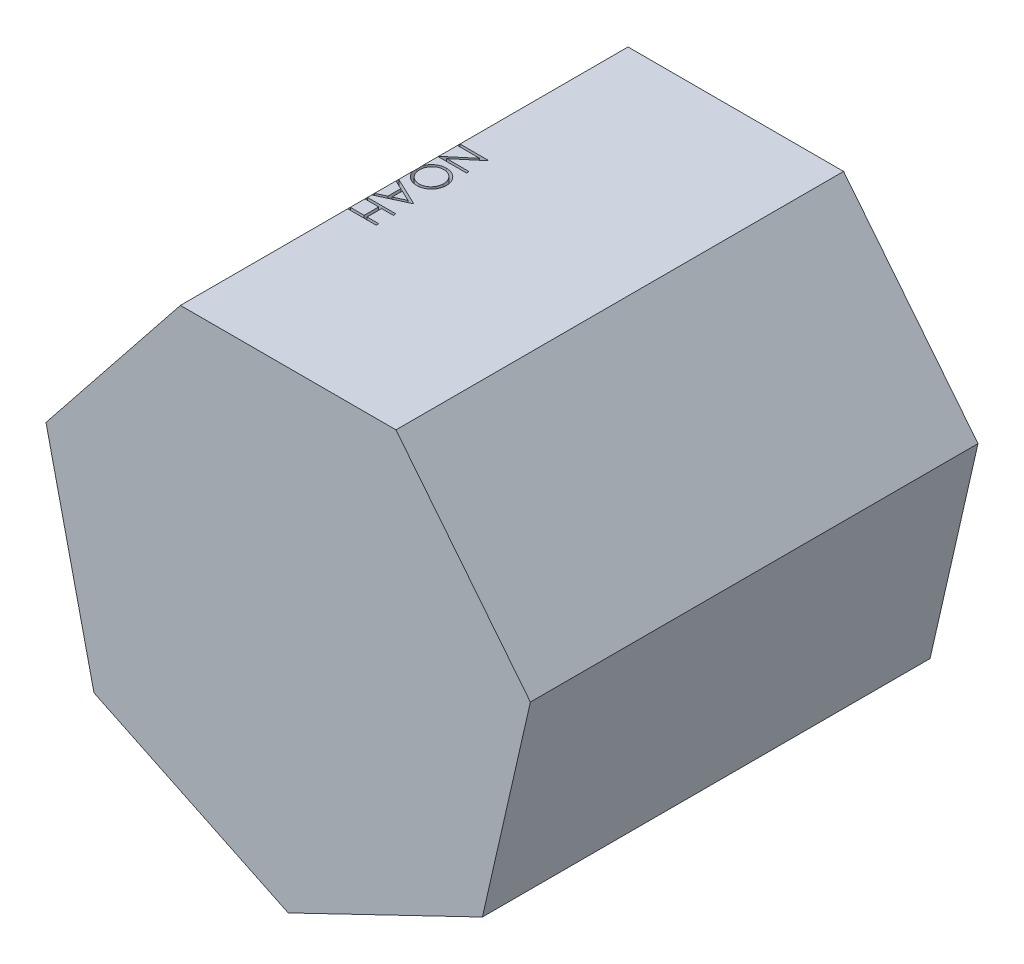
SolidWorks part; units mm, degrees
ref_plane "Front Plane" through (0, 0, 0) normal (0, 0, 1) x (1, 0, 0)
ref_plane "Top Plane" through (0, 0, 0) normal (0, 1, 0) x (1, 0, 0)
ref_plane "Right Plane" through (0, 0, 0) normal (1, 0, 0) x (0, 0, -1)
sketch "Sketch1" plane through (0, 0, 0) normal (0, 0, 1) x (1, 0, 0)
  line L1 (0, -110.9916) -> (86.7767, -69.2021)
  line L2 (86.7767, -69.2021) -> (108.2088, 24.698)
  line L3 (108.2088, 24.698) -> (48.1575, 100)
  line L4 (48.1575, 100) -> (-48.1575, 100)
  line L5 (-48.1575, 100) -> (-108.2088, 24.698)
  line L6 (-108.2088, 24.698) -> (-86.7767, -69.2021)
  line L7 (-86.7767, -69.2021) -> (0, -110.9916)
  circle A0 centre (0, 0) radius 100 construction
  dimension "D1" = 200
extrude "Boss-Extrude1" add sketch "Sketch1" along normal blind 200
sketch "Sketch2" plane through (-78.1831, 62.349, 0) normal (-0.7818, 0.6235, 0) x (0, 0, 1)
  text T0 "Andres" font "Century Gothic" height 20
extrude "Cut-Extrude1" cut sketch "Sketch2" against normal blind 1
sketch "Sketch4" plane through (-97.4928, -22.2521, 0) normal (-0.9749, -0.2225, 0) x (0, 0, 1)
  text T0 "Billy" font "Century Gothic" height 20
extrude "Cut-Extrude3" cut sketch "Sketch4" against normal blind 1
sketch "Sketch7" plane through (-43.3884, -90.0969, 0) normal (-0.4339, -0.901, 0) x (-0.901, 0.4339, 0)
  text T0 "ALEX" font "Century Gothic" height in points 72
extrude "Cut-Extrude5" cut sketch "Sketch7" against normal blind 2
sketch "Sketch8" plane through (0, 100, 0) normal (0, 1, 0) x (1, 0, 0)
  text T0 "NOAH" font "Century Gothic" height in points 48
extrude "Cut-Extrude6" cut sketch "Sketch8" against normal blind 10
